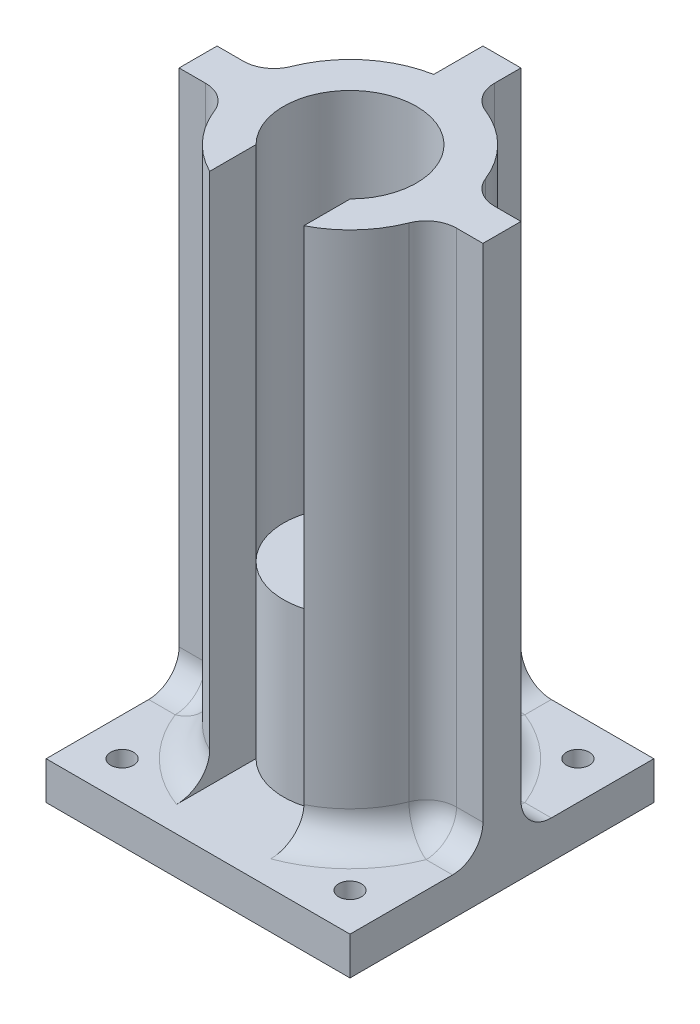
SolidWorks part; units mm, degrees
ref_plane "Front Plane" through (0, 0, 0) normal (0, 0, 1) x (1, 0, 0)
ref_plane "Top Plane" through (0, 0, 0) normal (0, 1, 0) x (1, 0, 0)
ref_plane "Right Plane" through (0, 0, 0) normal (1, 0, 0) x (0, 0, -1)
sketch "Sketch1" plane through (0, 0, 0) normal (0, 1, 0) x (1, 0, 0)
  line L1 (-25.4, -25.4) -> (25.4, -25.4)
  line L2 (-25.4, -25.4) -> (-25.4, 25.4)
  line L3 (-25.4, 25.4) -> (25.4, 25.4)
  line L4 (25.4, -25.4) -> (25.4, 25.4)
  line L5 (-25.4, -25.4) -> (25.4, 25.4) construction
  line L6 (-25.4, 25.4) -> (25.4, -25.4) construction
  point P0 (0, 0)
  dimension "D1" = 50.8
  dimension "D2" = 50.8
extrude "Boss-Extrude1" add sketch "Sketch1" along normal blind 6.35
sketch "Sketch2" plane through (0, 6.35, 0) normal (0, 1, 0) x (1, 0, 0)
  line L2 (-7.874, -7.8414) -> (-7.874, -15.5865)
  line L4 (7.874, -7.8414) -> (7.874, -15.5865)
  arc A0 (7.874, -7.8414) -> (-7.874, -7.8414) centre (0, 0) ccw
  arc A1 (7.874, -15.5865) -> (-7.874, -15.5865) centre (0, 0) ccw
  point P4 (0, -11.1125)
  dimension "D1" = 22.225
  dimension "D2" = 6.35
extrude "Boss-Extrude2" add sketch "Sketch2" along normal blind 88.9
sketch "Sketch3" plane through (0, 6.35, 0) normal (0, 1, 0) x (1, 0, 0)
  circle A0 centre (0, 0) radius 11.1125
extrude "Boss-Extrude3" add sketch "Sketch3" along normal blind 28.575
sketch "Sketch4" plane through (0, 6.35, 0) normal (0, 1, 0) x (1, 0, 0)
  line L0 (-25.4, 25.4) -> (-25.4, -25.4) construction
  line L1 (25.4, 25.4) -> (-25.4, 25.4) construction
  circle A0 centre (-19.05, 19.05) radius 1.905
  dimension "D2" = 3.81
  dimension "D1" = 6.35
  dimension "D3" = 6.35
extrude "Cut-Extrude1" cut sketch "Sketch4" against normal through all
pattern_circular "CirPattern1" count 4 over 360 about axis through (0, 95.25, 0) along (0, -1, 0) of "Cut-Extrude1"
sketch "Sketch5" plane through (0, 95.25, 0) normal (0, 1, 0) x (1, 0, 0)
  line L0 (25.4, 25.4) -> (-25.4, 25.4) construction
  line L1 (-3.175, 15.0908) -> (3.175, 15.0908)
  line L2 (-3.175, 15.0908) -> (-3.175, 25.4)
  line L3 (-3.175, 25.4) -> (3.175, 25.4)
  line L4 (3.175, 15.0908) -> (3.175, 25.4)
  line L5 (-17.4625, 0) -> (17.4625, 0) construction
  line L6 (17.4625, 0) -> (0, 17.4625) construction
  line L7 (25.4, -25.4) -> (25.4, 25.4) construction
  line L8 (14.0754, -3.175) -> (25.4, -3.175)
  line L9 (14.0754, -3.175) -> (14.0754, 3.175)
  line L10 (14.0754, 3.175) -> (25.4, 3.175)
  line L11 (25.4, -3.175) -> (25.4, 3.175)
  line L12 (0, 17.4625) -> (0, -16.5521) construction
  line L15 (-14.9157, -3.175) -> (-25.4, -3.175)
  line L16 (-14.9157, -3.175) -> (-14.9157, 3.175)
  line L17 (-14.9157, 3.175) -> (-25.4, 3.175)
  line L18 (-25.4, -3.175) -> (-25.4, 3.175)
  arc A0 (7.874, -15.5865) -> (-7.874, -15.5865) centre (0, 0) ccw construction
  arc A1 (7.874, -15.5865) -> (-7.874, -15.5865) centre (0, 0) ccw construction
  point P0 (0, 17.4625)
  point P10 (17.4625, 0)
  point P20 (-17.4625, 0)
  point P31 (0, 15.0908)
  point P32 (-14.9157, 0)
  point P33 (14.0754, 0)
  point P34 (0, 0)
  point P35 (0, 0)
  point P36 (0, 0)
  dimension "D1" = 6.35
  dimension "D2" = 6.35
  dimension "D3" = 6.35
extrude "Boss-Extrude4" add sketch "Sketch5" against normal up to surface (88.9 mm away) up to face at (17.145, 6.35, -19.05)
fillet "Fillet1" radius 5.08 14 edges at (17.1714, 50.8, -3.175) (3.175, 50.8, -17.1714) (3.175, 6.35, -21.2857) (12.3479, 6.35, -12.3479) (21.2857, 6.35, -3.175) (17.1714, 50.8, 3.175) (21.2857, 6.35, 3.175) (13.976, 6.35, 10.4694) (-17.1714, 50.8, -3.175) (-12.3479, 6.35, -12.3479) (-21.2857, 6.35, -3.175) (-13.976, 6.35, 10.4694) (-21.2857, 6.35, 3.175) (-17.1714, 50.8, 3.175)
